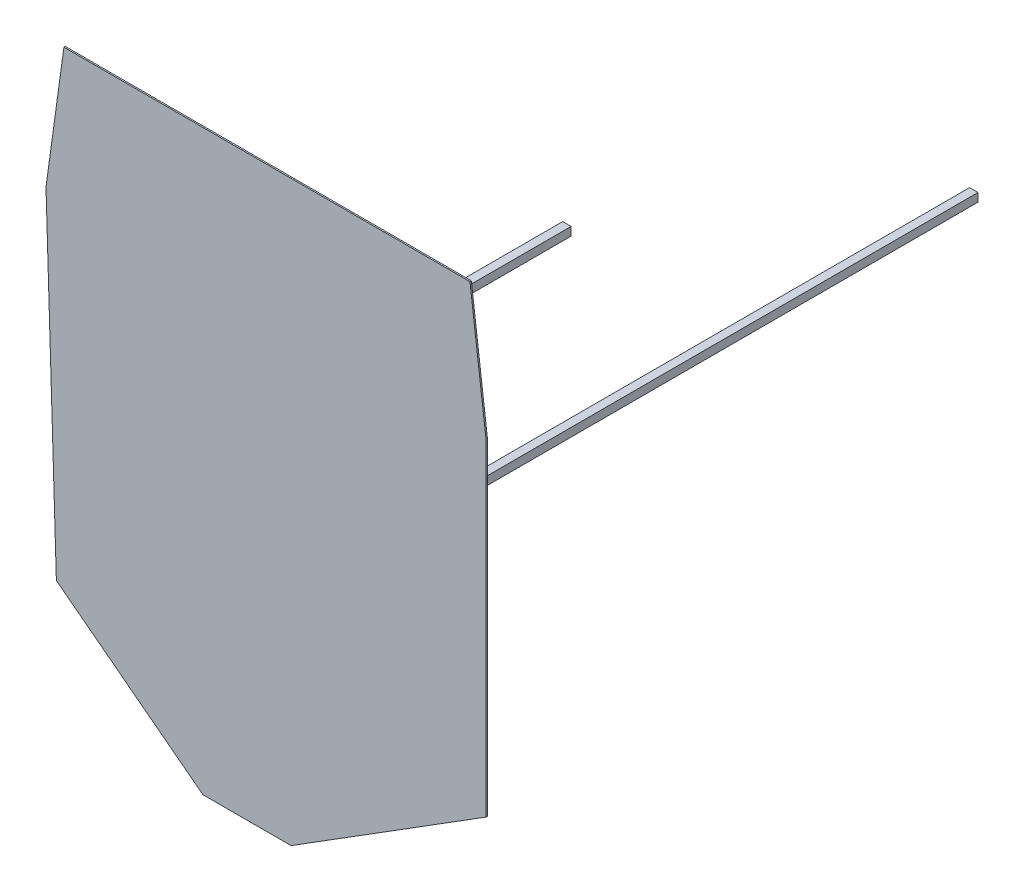
SolidWorks part; units mm, degrees
ref_plane "Front" through (0, 0, 0) normal (0, 0, 1) x (1, 0, 0)
ref_plane "Top" through (0, 0, 0) normal (0, 1, 0) x (1, 0, 0)
ref_plane "Right" through (0, 0, 0) normal (1, 0, 0) x (0, 0, -1)
sketch "Esquisse1" plane through (0, 0, 0) normal (0, 0, 1) x (1, 0, 0)
  line L1 (0, 0) -> (50, 0)
  line L2 (0, 0) -> (0, 50)
  line L3 (0, 50) -> (50, 50)
  line L4 (50, 0) -> (50, 50)
  dimension "D1" = 50
  dimension "D2" = 50
extrude "Boss.-Extru.1" add sketch "Esquisse1" along normal blind 5
sketch "Esquisse2" plane through (0, 0, 5) normal (0, 0, 1) x (1, 0, 0)
  line L0 (-5.6535, 9.3332) -> (57.2852, 53.4636)
  line L1 (57.2852, 53.4636) -> (231.6916, 53.4636)
  line L2 (231.6916, 53.4636) -> (285.9358, -3.0527)
  line L3 (285.9358, -3.0527) -> (284, -82.5096)
  line L4 (284, -82.5096) -> (207.7062, -129.7611)
  line L5 (207.7062, -129.7611) -> (50.4315, -129.7611)
  line L6 (50.4315, -129.7611) -> (-5.6535, -85.3866)
  line L7 (-5.6535, -85.3866) -> (-5.6535, 9.3332)
  line L8 (261, -129.7611) -> (23, -129.7611) construction
  line L9 (284, 24.7389) -> (284, -104.2611) construction
  point P2 (285.9358, -3.0527)
  point P5 (231.8631, 53.2848)
  point P10 (57.2852, 53.4636)
  point P11 (-5.6535, 9.3332)
  point P12 (-5.6535, -85.3866)
  point P13 (50.4315, -129.7611)
  point P16 (207.7062, -129.7611)
  point P17 (284, -82.5096)
extrude "Boss.-Extru.2" add sketch "Esquisse2" against normal up to vertex (5 mm away) up to point (0, 50, 0)
sketch "Esquisse3" plane through (0, 0, 0) normal (0, 0, -1) x (-1, 0, 0)
  line L0 (0, -121.7217) -> (6, -121.7217)
  line L1 (6, -121.7217) -> (6, -115.7217)
  line L2 (6, -115.7217) -> (0, -115.7217)
  line L4 (0, -115.7217) -> (0, -121.7217)
  line L6 (-284, 44.2389) -> (-290, 44.2389)
  line L7 (-284, 44.2389) -> (-284, 50.2389)
  line L8 (-284, 50.2389) -> (-290, 50.2389)
  line L9 (-290, 44.2389) -> (-290, 50.2389)
  dimension "D1" = 6
  dimension "D2" = 6
  dimension "D3" = 6
  dimension "D4" = 6
extrude "Boss.-Extru.3" add sketch "Esquisse3" along normal blind 350
sketch "Esquisse4" plane through (0, 0, 5) normal (0, 0, 1) x (1, 0, 0)
  line L0 (-5.5339, 170.1435) -> (283.89, 170.1435)
  line L1 (283.89, 170.1435) -> (295.4804, 77.4204)
  line L2 (295.4804, 77.4204) -> (295.4804, -154.5668)
  line L3 (295.4804, -154.5668) -> (156.3957, -241.7353)
  line L4 (156.3957, -241.7353) -> (93.5299, -241.7353)
  line L5 (93.5299, -241.7353) -> (-10.9091, -161.7784)
  line L6 (-10.9091, -161.7784) -> (-18.3001, 77.4204)
  line L7 (-18.3001, 77.4204) -> (-5.5339, 170.1435)
extrude "Boss.-Extru.4" add sketch "Esquisse4" along normal blind 1
